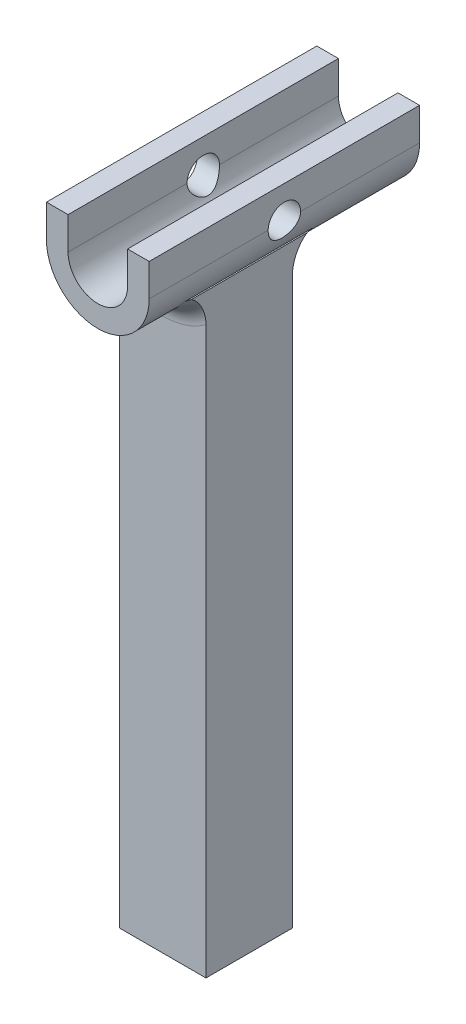
SolidWorks part; units mm, degrees
ref_plane "Front Plane" through (0, 0, 0) normal (0, 0, 1) x (1, 0, 0)
ref_plane "Top Plane" through (0, 0, 0) normal (0, 1, 0) x (1, 0, 0)
ref_plane "Right Plane" through (0, 0, 0) normal (1, 0, 0) x (0, 0, -1)
sketch "Sketch1" plane through (0, 0, 0) normal (0, 1, 0) x (1, 0, 0)
  line L1 (4, -15) -> (-4, -15)
  line L2 (4, -15) -> (4, -7)
  line L3 (4, -7) -> (-4, -7)
  line L4 (-4, -15) -> (-4, -7)
  point P4 (0, -7)
  dimension "D3" = 8
  dimension "D4" = 8
extrude "Boss-Extrude1" add sketch "Sketch1" against normal blind 55 contours L2 L3 L4 L1
sketch "Sketch2" plane through (0, 0, 0) normal (0, 0, 1) x (1, 0, 0)
  line L0 (-3.6183, 0) -> (3.4011, 0) construction
  line L1 (-8, 2) -> (8, 2) construction
  line L2 (-8, 2) -> (-4.4083, 5.5917)
  line L3 (8, 2) -> (3.6742, 6.3258)
  line L4 (-7.25, 2.75) -> (7.25, 2.75)
  line L5 (-4.75, 2.75) -> (-4.75, 5.75)
  line L6 (-4.75, 5.75) -> (4.75, 5.75)
  line L7 (4.75, 2.75) -> (4.75, 5.75)
  line L8 (2.75, 2.75) -> (2.75, 5.75)
  line L9 (-2.75, 2.75) -> (-2.75, 5.75)
  circle A0 centre (0, 2.75) radius 2.75
  circle A1 centre (0, 2.75) radius 4.75
  point P2 (-0.1086, 0)
  point P17 (0, 0)
  point P23 (0, 0)
  dimension "D1" = 0
  dimension "D8" = 5.5
  dimension "D9" = 3
  dimension "D3" = 2
  dimension "D4" = 45
  dimension "D5" = 45
  dimension "D6" = 8
  dimension "D7" = 8
  dimension "D2" = 2
extrude "Boss-Extrude2" add sketch "Sketch2" along normal blind 6 and the other way blind 19 from surface contours L4 A1 L6 L8 | L4 A1 A0 | L6 A1 L4 L9 | A1 L7 L6 | A1 L6 L5 | L3 L7 L6 region at (-4.4371, 5.0179, 0) region at (-3.6102, 4.0938, 0) region at (-3.75, 2.6438, 0) region at (4.4165, 4.9384, 0) region at (3.6102, 4.0938, 0) region at (4.5833, 5.5833, 0) starting at face at (0, -27.5, 15)
ref_plane "Plane1" [suppressed] through (5, 5, 0) normal (0.7071, 0.7071, 0) x (0.7071, -0.7071, 0)
ref_plane "Plane2" [suppressed] through (-5.6066, -5.6066, 0) normal (-0.7071, -0.7071, 0) x (0.7071, -0.7071, 0)
sketch "Sketch4" [suppressed] plane through (-5.6066, -5.6066, 0) normal (-0.7071, -0.7071, 0) x (0.7071, -0.7071, 0)
  line L0 (-2.7221, 7) -> (-2.7221, 15) construction
  circle A0 centre (-4.7221, 11) radius 1.25
  point P4 (-2.7221, 11)
  dimension "D1" = 2
  dimension "D2" = 2.5
extrude "Cut-Extrude1" [suppressed] cut sketch "Sketch4" against normal through all
mirror "Mirror1" [suppressed] about plane through (0, 0, 0) normal (1, 0, 0)
fillet "Fillet1" radius 2 2 edges at (0, -2, 7) (0, -2, 15)
sketch "Sketch6" plane through (4.75, 0, 0) normal (1, 0, 0) x (0, 0, -1)
  line L1 (4, 2.75) -> (-21, 2.75) construction
  circle A0 centre (-8.5, 2.75) radius 1.5
  point P2 (0, 0)
extrude "Cut-Extrude2" cut sketch "Sketch6" against normal through all both and the other way through all
